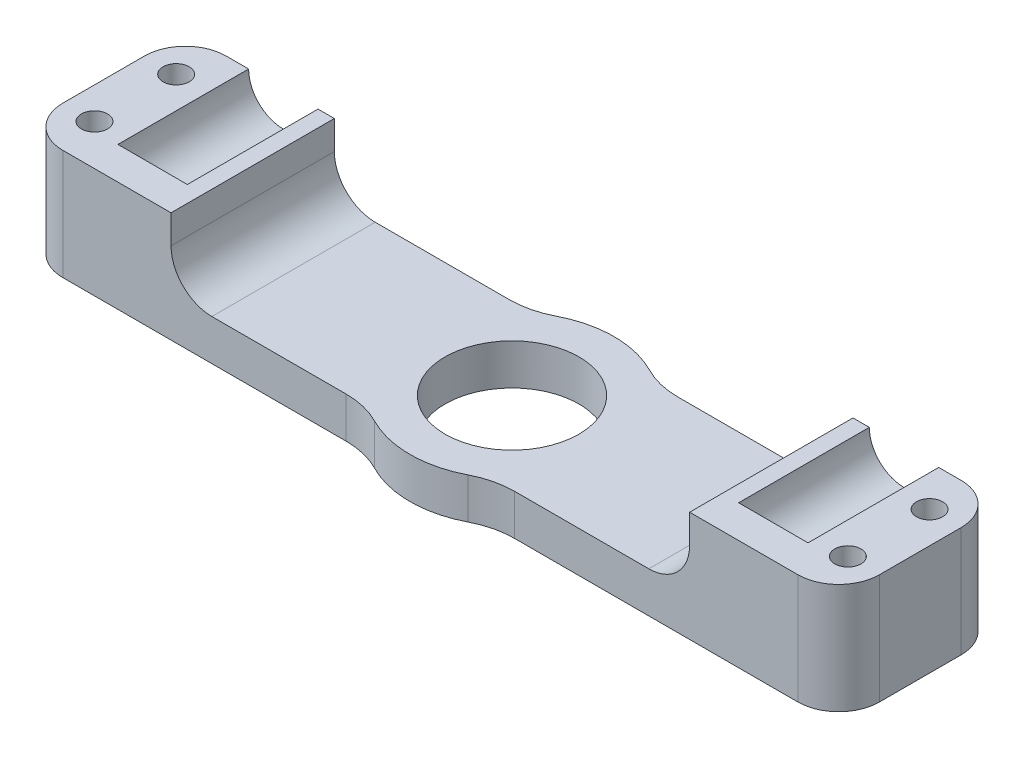
SolidWorks part; units mm, degrees
ref_plane "Front Plane" through (0, 0, 0) normal (0, 0, 1) x (1, 0, 0)
ref_plane "Top Plane" through (0, 0, 0) normal (0, 1, 0) x (1, 0, 0)
ref_plane "Right Plane" through (0, 0, 0) normal (1, 0, 0) x (0, 0, -1)
sketch "Sketch1" plane through (0, 0, 0) normal (0, 1, 0) x (1, 0, 0)
  line L0 (-44, 0) -> (-44, -44) construction
  line L1 (-44, -44) -> (44, -44) construction
  line L2 (44, -44) -> (44, 0) construction
  line L4 (-44, -10) -> (44, -10)
  line L5 (-44, -10) -> (-44, 10)
  line L6 (-44, 10) -> (44, 10)
  line L7 (44, -10) -> (44, 10)
  line L8 (-44, -10) -> (44, 10) construction
  line L9 (-44, 10) -> (44, -10) construction
  arc A0 (44, 0) -> (-44, 0) centre (0, 0) ccw construction
  dimension "D1" = 88
  dimension "D2" = 88
  dimension "D3" = 20
extrude "Boss-Extrude1" add sketch "Sketch1" along normal blind 27
sketch "Sketch2" plane through (0, 0, 10) normal (0, 0, 1) x (1, 0, 0)
  line L1 (-1044, 13.5) -> (48956, 13.5) construction
  line L2 (0, -1000) -> (0, 49000) construction
  line L3 (-44, 27) -> (-44, 0) construction
  circle A0 centre (-38, 13.5) radius 4.25
  circle A1 centre (38, 13.5) radius 4.25
  point P2 (-44, 13.5)
  dimension "D1" = 8.5
  dimension "D2" = 6
extrude "Cut-Extrude1" cut sketch "Sketch2" against normal through all
sketch "Sketch7" plane through (0, 27, 0) normal (0, 1, 0) x (1, 0, 0)
  circle A0 centre (0, 0) radius 12.5
  dimension "D1" = 25
extrude "Boss-Extrude2" add sketch "Sketch7" against normal up to surface (27 mm away) up to face at (0, 0, 0)
sketch "Sketch4" plane through (0, 27, 0) normal (0, 1, 0) x (1, 0, 0)
  circle A0 centre (0, 0) radius 8.2
  dimension "D1" = 16.4
extrude "Cut-Extrude3" cut sketch "Sketch4" against normal through all
fillet "Fillet2" radius 10 4 edges at (7.5, 13.5, 10) (-7.5, 13.5, 10) (7.5, 13.5, -10) (-7.5, 13.5, -10)
sketch "Sketch9" plane through (-44, 0, 0) normal (-1, 0, 0) x (0, 0, 1)
  line L5 (-1017.3065, 27) -> (48982.6935, 27) construction
  line L6 (-1016.9067, 13.5) -> (48983.0933, 13.5) construction
  line L7 (-12.5, 27) -> (-12.5, 0) construction
  line L8 (-10, 27) -> (10, 27) construction
  line L9 (12.5, 0) -> (12.5, 27) construction
  line L10 (-13.5, 27) -> (13.5, 27)
  line L11 (-13.5, 27) -> (-13.5, 13.5)
  line L12 (-13.5, 13.5) -> (13.5, 13.5)
  line L13 (13.5, 27) -> (13.5, 13.5)
  point P3 (-12.5, 13.5)
  dimension "D1" = 1
  dimension "D2" = 1
extrude "Cut-Extrude4" cut sketch "Sketch9" against normal through all
sketch "Sketch10" plane through (0, 0, 0) normal (0, 0, 1) x (1, 0, 0)
  line L0 (44, 0) -> (10.3078, 0) construction
  line L1 (31.75, 15.5) -> (-31.75, 15.5)
  line L2 (31.75, 15.5) -> (31.75, 5)
  line L3 (31.75, 5) -> (-31.75, 5)
  line L4 (-31.75, 15.5) -> (-31.75, 5)
  line L5 (10.3078, 13.5) -> (33.75, 13.5) construction
  dimension "D1" = 5
  dimension "D2" = 2
  dimension "D3" = 2
  dimension "D4" = 2
extrude "Cut-Extrude5" cut sketch "Sketch10" against normal through all and the other way through all
fillet "Fillet3" radius 5 2 edges at (-31.75, 5, 0) (31.75, 5, 0)
sketch "Sketch11" plane through (44, 0, 0) normal (1, 0, 0) x (0, 0, -1)
  line L4 (10, 0) -> (10, 13.5)
  line L5 (10, 13.5) -> (-10, 13.5)
  line L6 (-10, 13.5) -> (-10, 0)
  line L7 (-10, 0) -> (10, 0)
  line L8 (10, 0) -> (10, 13.5)
  line L9 (10, 13.5) -> (-10, 13.5)
  line L10 (-10, 13.5) -> (-10, 0)
  line L11 (-10, 0) -> (10, 0)
  dimension "D1" = 0
extrude "Boss-Extrude3" add sketch "Sketch11" along normal blind 6
sketch "Sketch12" plane through (0, 13.5, 0) normal (0, 1, 0) x (1, 0, 0)
  line L0 (46.125, -10) -> (46.125, 10) construction
  line L1 (50, -10) -> (42.25, -10) construction
  line L2 (42.25, 10) -> (50, 10) construction
  circle A0 centre (46.125, -5) radius 1.6
  circle A1 centre (46.125, 5) radius 1.6
  dimension "D1" = 3.2
  dimension "D2" = 5
  dimension "D3" = 5
extrude "Cut-Extrude6" cut sketch "Sketch12" against normal through all
mirror "Mirror1" about plane through (0, 0, 0) normal (1, 0, 0) of "Boss-Extrude3", "Cut-Extrude6"
fillet "Fillet4" radius 5 4 edges at (-50, 6.75, 10) (-50, 6.75, -10) (50, 6.75, 10) (50, 6.75, -10)
sketch "Sketch13" plane through (0, 0, 10) normal (0, 0, 1) x (1, 0, 0)
  line L0 (-42.25, 13.5) -> (-33.75, 13.5)
  line L1 (33.75, 13.5) -> (42.25, 13.5)
  arc A0 (33.75, 13.5) -> (42.25, 13.5) centre (38, 13.5) ccw construction
  arc A1 (-42.25, 13.5) -> (-33.75, 13.5) centre (-38, 13.5) ccw construction
  arc A2 (33.75, 13.5) -> (42.25, 13.5) centre (38, 13.5) ccw
  arc A3 (-42.25, 13.5) -> (-33.75, 13.5) centre (-38, 13.5) ccw
extrude "Boss-Extrude4" add sketch "Sketch13" against normal blind 4
